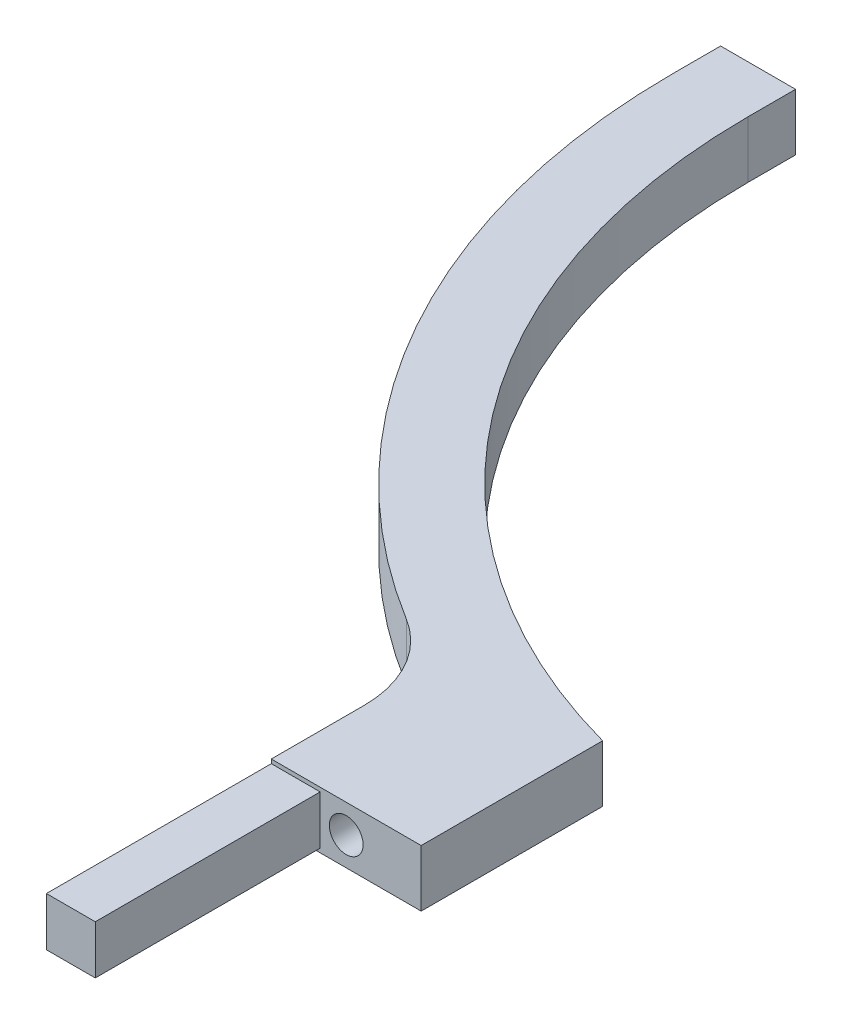
SolidWorks part; units mm, degrees
ref_plane "Front Plane" through (0, 0, 0) normal (0, 0, 1) x (1, 0, 0)
ref_plane "Top Plane" through (0, 0, 0) normal (0, 1, 0) x (1, 0, 0)
ref_plane "Right Plane" through (0, 0, 0) normal (1, 0, 0) x (0, 0, -1)
sketch "Sketch4" plane through (0, 0, 0) normal (0, 1, 0) x (1, 0, 0)
  line L0 (-189.6, 0) -> (-169.6, 0)
  line L4 (-44.8145, -163.5721) -> (-44.8145, -211.9792)
  line L5 (-44.8145, -211.9792) -> (-84.8, -211.9792)
  line L7 (-169.6, 0) -> (0, 0) construction
  line L8 (-84.8, 0) -> (-84.8, -264.5922) construction
  line L11 (-84.8, -169.5792) -> (-84.8, -211.9792)
  arc A0 (-169.6, 0) -> (-44.8145, -163.5721) centre (0, 0) ccw
  arc A1 (-189.6, 0) -> (-84.8, -169.5792) centre (0, 0) ccw
  point P11 (-84.8, -211.9792)
  dimension "D1" = 169.6
  dimension "D3" = 20
  dimension "D5" = 42.4
  dimension "D2" = 189.6
extrude "Boss-Extrude1" add sketch "Sketch4" against normal blind 15.1643
sketch "Sketch5" plane through (0, 0, 211.9792) normal (0, 0, 1) x (1, 0, 0)
  line L0 (-64.8073, 0) -> (-64.8073, -15.1643) construction
  line L1 (-84.8, 0) -> (-44.8145, 0) construction
  line L2 (-84.8, -15.1643) -> (-44.8145, -15.1643) construction
  circle A0 centre (-64.8073, -7.5821) radius 4.505
  dimension "D1" = 9.01
extrude "Cut-Extrude1" cut sketch "Sketch5" against normal blind 30 contours A0
sketch "Sketch6" plane through (0, 0, 0) normal (0, 0, -1) x (-1, 0, 0)
  line L1 (169.6, 0) -> (189.6, 0)
  line L2 (169.6, 0) -> (169.6, -15.1643)
  line L3 (169.6, -15.1643) -> (189.6, -15.1643)
  line L4 (189.6, 0) -> (189.6, -15.1643)
extrude "Boss-Extrude2" add sketch "Sketch6" along normal blind 12.7
fillet "Fillet1" radius 30 1 edges at (-84.8, -7.5821, 169.5792)
sketch "Sketch7" plane through (0, 0, 211.9792) normal (0, 0, 1) x (1, 0, 0)
  line L0 (-84.8, 0) -> (-84.8, -15.1643) construction
  line L1 (-84.8, -1.0821) -> (-71.76, -1.0821)
  line L2 (-84.8, -1.0821) -> (-84.8, -14.0821)
  line L3 (-84.8, -14.0821) -> (-71.76, -14.0821)
  line L4 (-71.76, -1.0821) -> (-71.76, -14.0821)
  line L5 (-84.8, -7.5821) -> (-44.8145, -7.5821) construction
  line L6 (-44.8145, -15.1643) -> (-44.8145, 0) construction
  dimension "D1" = 13
  dimension "D2" = 13.04
extrude "Boss-Extrude3" add sketch "Sketch7" along normal blind 60
sketch "Sketch8" plane through (-84.8, 0, 0) normal (-1, 0, 0) x (0, 0, 1)
  line L0 (211.9792, -1.0821) -> (211.9792, -14.0821) construction
  line L1 (211.9792, -7.5821) -> (231.9792, -7.5821) construction
  line L2 (231.9792, -7.5821) -> (251.9792, -7.5821) construction
  circle A0 centre (231.9792, -7.5821) radius 1.5
  circle A1 centre (251.9792, -7.5821) radius 1.5
  dimension "D1" = 3
  dimension "D2" = 3
  dimension "D3" = 20
  dimension "D4" = 20
extrude "Cut-Extrude2" cut sketch "Sketch8" against normal blind 10
equation "\"Waist\"= 33.92cm"
equation "\"D1@Sketch4\"=\"Waist\"/2"
equation "\"D3@Sketch4\" = \"frontplate_thickness\""
equation "\"D5@Sketch4\"=(\"Waist\"/2)*0.25"
equation "\"D1@Boss-Extrude1\" = \"frontplate_height\""
equation "\"D1@Sketch5\"=\"Dowelpin_diameter\"+0.01"
equation "\"D1@Boss-Extrude2\"=12.7mm"
equation "\"backplate_height\"=262.50000000"
equation "\"D2@Sketch4\"= ( \"Waist\" / 2 ) + \"frontplate_thickness\""
equation "\"Dowelpin_diameter\"= 9mm"
equation "\"frontplate_thickness\"=20.00000000"
equation "\"frontplate_height\"=15.16426412"
equation "\"backplate_thickness\"=14.23743012"
equation "\"backplate_width\"=100.00000000"
equation "\"hinge_diameter\"=8.42439351"
equation "\"hinge_height\"=15.16426412"
equation "\"adjustment_thickness\"=5.13421512"
equation "\"adjustment_height\"=26.25000000"
equation "\"Padding_Area1\"=2482.39529083"
equation "\"Padding_Area2\"=2482.39529083"
equation "\"Padding_Area3\"=551.64339796"
